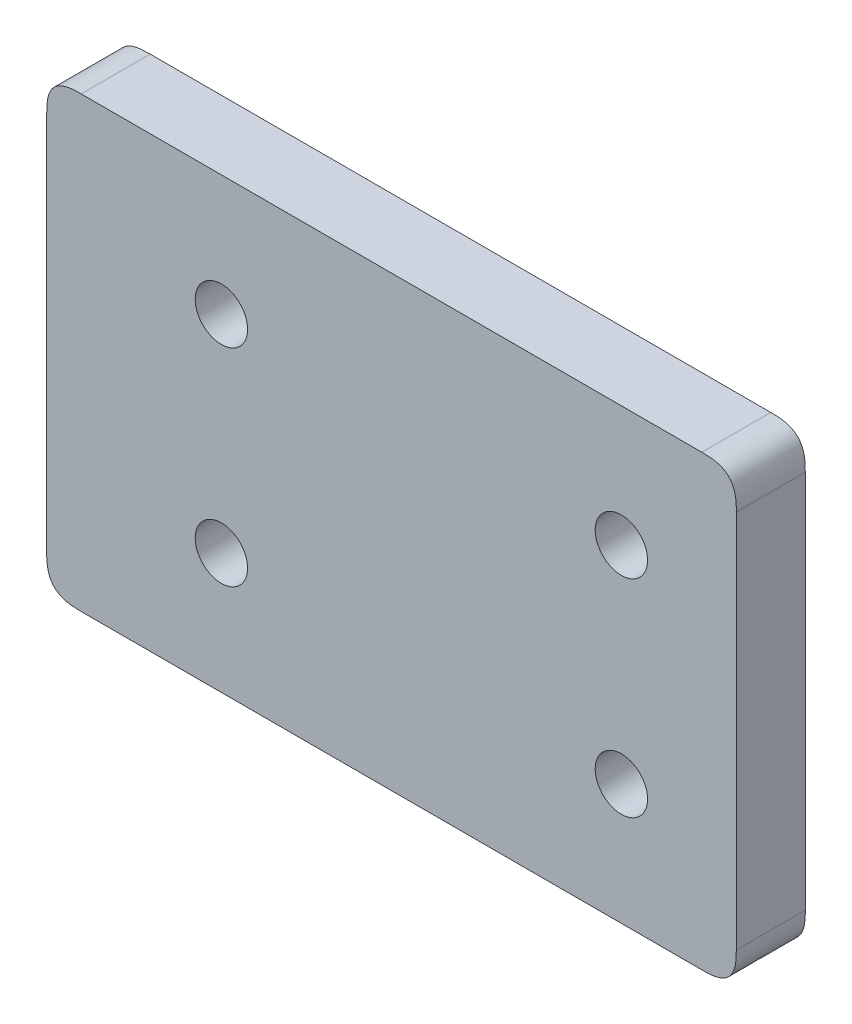
SolidWorks part; units mm, degrees
ref_plane "Front Plane" through (0, 0, 0) normal (0, 0, 1) x (1, 0, 0)
ref_plane "Top Plane" through (0, 0, 0) normal (0, 1, 0) x (1, 0, 0)
ref_plane "Right Plane" through (0, 0, 0) normal (1, 0, 0) x (0, 0, -1)
sketch "Sketch1" plane through (0, 0, 0) normal (0, 0, 1) x (1, 0, 0)
  line L5 (12.7, 3.175) -> (76.2, 3.175)
  line L6 (12.7, 3.175) -> (12.7, 44.45)
  line L7 (12.7, 44.45) -> (76.2, 44.45)
  line L8 (76.2, 3.175) -> (76.2, 44.45)
  dimension "D1" = 41.275
  dimension "D2" = 63.5
  dimension "D3" = 12.7
  dimension "D4" = 3.175
extrude "Boss-Extrude1" add sketch "Sketch1" along normal blind 6.35
sketch "Sketch3" plane through (0, 0, 6.35) normal (0, 0, 1) x (1, 0, 0)
  line L0 (65.6155, 14.2875) -> (55.4555, 14.2875) construction
  line L1 (65.6155, 33.3375) -> (55.4555, 33.3375) construction
  circle A4 centre (65.6155, 14.2875) radius 2.413
  circle A5 centre (65.6155, 33.3375) radius 2.413
  circle A6 centre (28.7855, 14.2875) radius 2.413
  circle A7 centre (28.7855, 33.3375) radius 2.413
  circle A8 centre (55.4555, 33.3375) radius 2.413
  circle A9 centre (55.4555, 14.2875) radius 2.413
  dimension "D1" = 10.16
extrude "Cut-Extrude1" cut sketch "Sketch3" against normal through all and the other way through all contours A5 | A7 | A6 | A4 region at (65.6155, 14.2875, 6.35) region at (65.6155, 33.3375, 6.35) region at (28.7855, 14.2875, 6.35) region at (28.7855, 33.3375, 6.35)
fillet "Fillet1" radius 3.175 4 edges at (12.7, 3.175, 3.175) (12.7, 44.45, 3.175) (76.2, 3.175, 3.175) (76.2, 44.45, 3.175) curvature continuous yes
